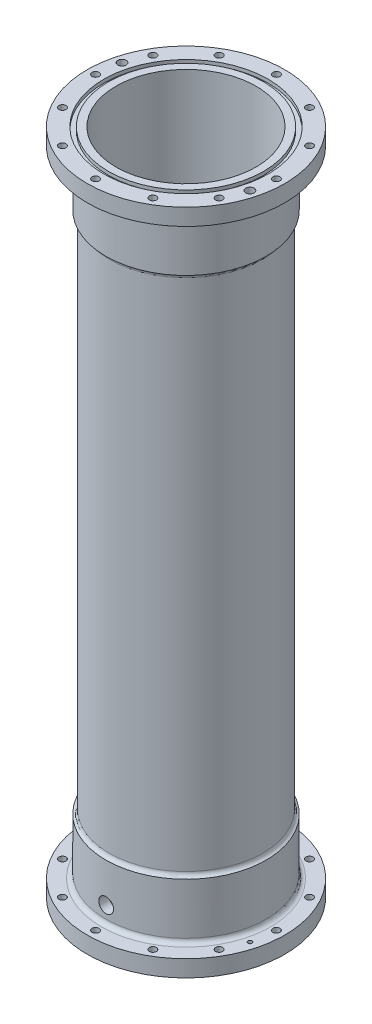
SolidWorks part; units mm, degrees
material "7075-T6 (SN)"
ref_plane "Front Plane" through (0, 0, 0) normal (0, 0, 1) x (1, 0, 0)
ref_plane "Top Plane" through (0, 0, 0) normal (0, 1, 0) x (1, 0, 0)
ref_plane "Right Plane" through (0, 0, 0) normal (1, 0, 0) x (0, 0, -1)
sketch "Sketch2" plane through (0, 0, 0) normal (0, 1, 0) x (1, 0, 0)
  circle A0 centre (0, 0) radius 40
  circle A1 centre (0, 0) radius 43.815
  dimension "D1" = 87.63
  dimension "D2" = 80
extrude "Base Cylinder" add sketch "Sketch2" along normal blind 381
sketch "Sketch3" plane through (0, 0, 0) normal (0, -1, 0) x (1, 0, 0)
  circle A0 centre (0, 0) radius 40
  circle A1 centre (0, 0) radius 56.3562
  dimension "D1" = 112.7125
  dimension "D2" = 80
extrude "Aft Flange" add sketch "Sketch3" against normal blind 9.525
sketch "Sketch6" plane through (0, 0, 0) normal (0, -1, 0) x (1, 0, 0)
  circle A0 centre (0, 0) radius 46.9011
  circle A1 centre (0, 0) radius 44.2849
  dimension "D1" = 93.8022
  dimension "D2" = 88.5698
extrude "Aft O-Ring" cut sketch "Sketch6" against normal blind 1.9812
sketch "Sketch33" plane through (0, 9.525, 0) normal (0, 1, 0) x (1, 0, 0)
  circle A0 centre (0, 0) radius 43.815
  circle A1 centre (0, 0) radius 45.72
  dimension "D1" = 87.63
  dimension "D2" = 91.44
extrude "CriticalBoss" add sketch "Sketch33" along normal blind 31.75
fillet "Fillet1" radius 2.54 2 edges at (0, 9.525, -45.72) (0, 41.275, 43.815)
sketch "Sketch For Bolt Holes" plane through (0, 0, 0) normal (0, -1, 0) x (1, 0, 0)
  circle A0 centre (-51.6255, 0) radius 1.5875
  circle A1 centre (-44.709, 25.8128) radius 1.5875
  circle A2 centre (-25.8128, 44.709) radius 1.5875
  circle A3 centre (0, 51.6255) radius 1.5875
  circle A4 centre (25.8127, 44.709) radius 1.5875
  circle A5 centre (44.709, 25.8128) radius 1.5875
  circle A6 centre (51.6255, 0) radius 1.5875
  circle A7 centre (44.709, -25.8127) radius 1.5875
  circle A8 centre (25.8128, -44.709) radius 1.5875
  circle A9 centre (0, -51.6255) radius 1.5875
  circle A10 centre (-25.8127, -44.709) radius 1.5875
  circle A11 centre (-44.709, -25.8128) radius 1.5875
  point P36 (0, 0)
  dimension "D2" = 3.175
  dimension "D1" = 51.6255
  dimension "D3" = 12
hole_wizard "Bolt Circle" positions "Sketch8" profile "Sketch9" tap size "#10-32" standard "ANSI Inch" end condition up to next
sketch "Sketch8" plane through (0, 0, 0) normal (0, -1, 0) x (-1, 0, 0)
  point P0 (-25.8127, -44.709)
  point P3 (-44.709, -25.8128)
  point P6 (-51.6255, 0)
  point P9 (-44.709, 25.8127)
  point P12 (-25.8128, 44.709)
  point P15 (0, 51.6255)
  point P18 (25.8127, 44.709)
  point P21 (44.709, 25.8128)
  point P24 (51.6255, 0)
  point P27 (44.709, -25.8128)
  point P30 (25.8128, -44.709)
  point P33 (0, -51.6255)
  point P36 (-25.8127, -44.709)
  point P38 (-44.709, -25.8128)
  point P40 (-51.6255, 0)
sketch "Sketch9" plane through (25.8127, 0, 44.709) normal (1, 0, 0) x (0, 0, -1)
  line L0 (0, 0) -> (0, 9.525)
  line L1 (0, 9.525) -> (2.0193, 9.525)
  line L2 (2.0193, 9.525) -> (2.0193, 0)
  line L5 (2.0193, 0) -> (0, 0)
  line L11 (0, -6.35) -> (0, 107.95) construction
  dimension "Thread Major Dia." = 4.0386
  dimension "Thru Tap Drill Depth" = 9.525
sketch "Dowel Hole Sketch" plane through (0, 0, 0) normal (0, -1, 0) x (1, 0, 0)
  line L0 (0, 0) -> (-51.6255, 0) construction
  line L1 (0, 0) -> (-49.8664, -13.3617) construction
  line L2 (0, 0) -> (0, -51.6255) construction
  line L3 (0, 0) -> (49.8664, 13.3617) construction
  circle A0 centre (0, 0) radius 51.6255
  circle A1 centre (-49.8664, -13.3617) radius 4.6172
  circle A2 centre (49.8664, 13.3617) radius 3.4532
  dimension "D1" = 15
hole_wizard "Hole1" positions "Sketch14" profile "Sketch12" legacy end condition up to next
sketch "Sketch14" plane through (0, 0, 0) normal (0, -1, 0) x (-1, 0, 0)
  point P0 (49.8664, 13.3617)
  point P3 (-49.8664, -13.3617)
sketch "Sketch12" plane through (-49.8664, 0, -13.3617) normal (1, 0, 0) x (0, 0, -1)
  line L0 (0, 0) -> (0, 9.525)
  line L1 (0, 9.525) -> (1.1906, 9.525)
  line L2 (1.1906, 9.525) -> (1.1906, 4.7625)
  line L3 (1.1906, 4.7625) -> (2.3813, 4.7625)
  line L4 (2.3813, 4.7625) -> (2.3813, 0)
  line L5 (2.3813, 0) -> (0, 0)
  line L6 (0, 110) -> (0, -10) construction
  dimension "Diameter" = 2.3813
  dimension "Depth" = 9.525
  dimension "C-Bore Diameter" = 4.7625
  dimension "C-Bore Depth" = 4.7625
ref_plane "Hoop Mid-Plane" through (0, 190.5, 0) normal (0, 1, 0) x (1, 0, 0)
ref_plane "PressureTapHolePlane" through (0, 0, 45.72) normal (0, 0, 1) x (1, 0, 0)
ref_plane "TemperatureTapPlane" through (0, 0, -45.72) normal (0, 0, 1) x (1, 0, 0)
sketch "ThermoHole" plane through (0, 0, -45.72) normal (0, 0, 1) x (1, 0, 0)
  line L0 (-56.3562, 0) -> (56.3562, 0) construction
  circle A0 centre (0, 19.05) radius 3.175
  dimension "D1" = 19.05
  dimension "D2" = 6.35
hole_wizard "1/8 NPT Tapped ThermocoupleHole" positions "Sketch43" profile "Sketch44" size "1/8" standard "ANSI Inch"
sketch "Sketch43" plane through (0, 0, -45.72) normal (0, 0, 1) x (1, 0, 0)
  line L0 (-56.3562, 0) -> (56.3562, 0) construction
  point P0 (0, 19.05)
  dimension "D1" = 19.05
sketch "Sketch44" plane through (0, 19.05, -45.72) normal (1, 0, 0) x (0, 1, 0)
  line L0 (0, 0) -> (0, 14.2135)
  line L1 (4.2164, 11.68) -> (0, 14.2135)
  line L2 (-4.2164, 11.68) -> (0, 14.2135) construction
  line L3 (4.2164, 11.68) -> (4.2164, 6.86)
  line L4 (4.2164, 6.86) -> (4.5374, 6.86)
  line L5 (4.5374, 6.86) -> (4.7428, 0)
  line L6 (-4.5374, 6.86) -> (-4.7428, 0) construction
  line L7 (4.7428, 0) -> (0, 0)
  line L8 (0, -6.35) -> (0, 107.95) construction
  line L11 (-4.2164, 6.86) -> (-4.5374, 6.86) construction
  dimension "Tap Drill Dia." = 8.4328
  dimension "Tap Drill Depth" = 11.68
  dimension "Thread Dia." = 9.4856
  dimension "Thread Angle" = 3.43
  dimension "Thread Depth" = 6.86
  dimension "Drill Angle" = 118
cosmetic thread "Hole Thread3" [suppressed] parameters "D1"=5.9812, "D2"=10.2832
hole_wizard "3/8-24 Tapped Hole1" positions "Sketch48" profile "Sketch49" tap size "3/8-24" standard "ANSI Inch" end condition up to next
sketch "Sketch48" plane through (0, 0, 45.72) normal (0, 0, 1) x (1, 0, 0)
  line L0 (-56.3562, 0) -> (56.3562, 0) construction
  point P0 (0, 19.05)
  dimension "D1" = 19.05
sketch "Sketch49" plane through (0, 19.05, 45.72) normal (1, 0, 0) x (0, -1, 0)
  line L0 (0, 0) -> (0, 5.72)
  line L1 (0, 5.72) -> (4.2164, 5.72)
  line L2 (4.2164, 5.72) -> (4.2164, 0)
  line L5 (4.2164, 0) -> (0, 0)
  line L11 (0, -6.35) -> (0, 107.95) construction
  dimension "Thru Tap Drill Dia." = 8.4328
  dimension "Thru Tap Drill Depth" = 5.72
cosmetic thread "Hole Thread2" parameters "D2"=9.525
mirror "Mirror1" about plane through (0, 190.5, 0) normal (0, 1, 0) of "Aft Flange", "Aft O-Ring", "Bolt Circle", "Hole1", "CriticalBoss", "Fillet1"
